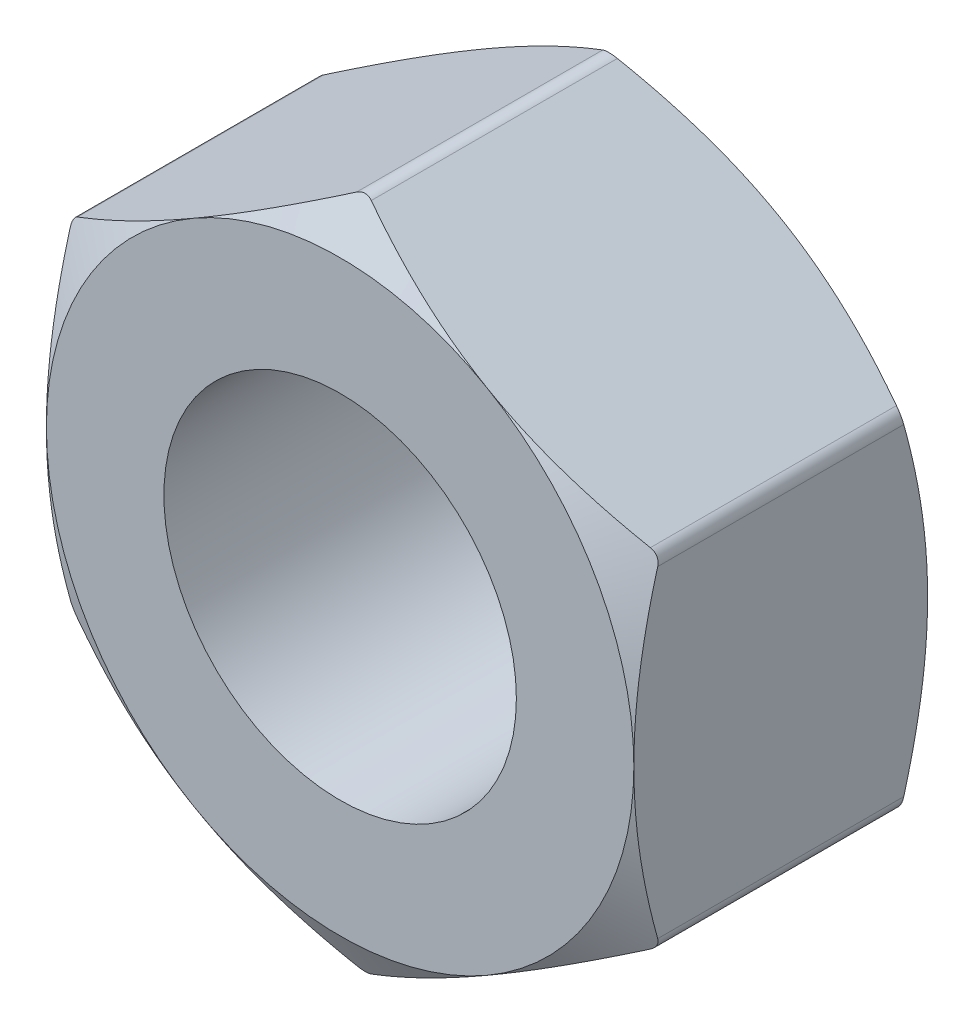
SolidWorks part; units mm, degrees
ref_plane "Front" through (0, 0, 0) normal (0, 0, 1) x (1, 0, 0)
ref_plane "Top" through (0, 0, 0) normal (0, 1, 0) x (1, 0, 0)
ref_plane "Right" through (0, 0, 0) normal (1, 0, 0) x (0, 0, -1)
sketch "Sketch1" plane through (0, 0, 0) normal (0, 0, 1) x (1, 0, 0)
  line L0 (0, 3) -> (0, 2) construction
  line L1 (-5, 2.8868) -> (-5, -2.8868)
  line L2 (-5, -2.8868) -> (0, -5.7735)
  line L3 (0, -5.7735) -> (5, -2.8868)
  line L4 (5, -2.8868) -> (5, 2.8868)
  line L5 (5, 2.8868) -> (0, 5.7735)
  line L6 (0, 5.7735) -> (-5, 2.8868)
  circle A0 centre (0, 0) radius 5 construction
  circle A1 centre (0, 0) radius 3 construction
  point P10 (0, 3)
  dimension "Width" = 10
  dimension "Thread Size" = 6
  dimension "Thread Pitch" = 1
sketch "Sketch2" plane through (0, 0, 0) normal (1, 0, 0) x (0, 0, -1)
  line L0 (-2.5, 0) -> (2.5, 0) construction
  line L1 (-2.5, 5.7735) -> (2.5, 5.7735) construction
  dimension "Height" = 5
sketch "Sketch15" plane through (0, 0, 0) normal (0, 0, 1) x (1, 0, 0)
  line L1 (0, 5.7735) -> (-5, 2.8868)
  line L2 (-5, 2.8868) -> (-5, -2.8868)
  line L3 (-5, -2.8868) -> (0, -5.7735)
  line L4 (0, -5.7735) -> (5, -2.8868)
  line L5 (5, -2.8868) -> (5, 2.8868)
  line L6 (5, 2.8868) -> (0, 5.7735)
  circle A0 centre (0, 0) radius 5 construction
extrude "Boss-Extrude2" add sketch "Sketch15" along normal mid plane 5
sketch "Sketch16" plane through (0, 0, 0) normal (0, 0, 1) x (1, 0, 0)
  circle A0 centre (0, 0) radius 3 construction
  circle A1 centre (0, 0) radius 3
sketch "Sketch4" [suppressed] plane through (0, 0, -2.5) normal (0, 0, -1) x (-1, 0, 0)
  circle A0 centre (0, 0) radius 3 construction
  circle A1 centre (0, 0) radius 3
extrude "Cut-Extrude4" cut sketch "Sketch16" against normal through all both and the other way through all
sketch "Sketch7" plane through (0, 0, 2.5) normal (0, 0, 1) x (1, 0, 0)
  circle A0 centre (0, 0) radius 5 construction
  circle A1 centre (0, 0) radius 5
extrude "Cut-Extrude5" cut sketch "Sketch7" against normal through all draft 60 flip side to cut
mirror "Mirror4" about plane through (0, 0, 0) normal (0, 0, 1) of "Cut-Extrude5"
fillet "Fillet2" radius 0.25 6 edges at (-5, 2.8868, 0) (-5, -2.8868, 0) (0, -5.7735, 0) (5, -2.8868, 0) (5, 2.8868, 0) (0, 5.7735, 0)
sketch "Sketch8" plane through (0, 0, 2.5) normal (0, 0, 1) x (1, 0, 0)
  line L0 (0.7765, -2.8978) -> (0, 0) construction
  line L2 (0, 3) -> (0, 2) construction
  circle A0 centre (0, 0) radius 3 construction
  point P0 (0.7765, -2.8978)
  dimension "D1" = 15
sketch "Sketch13" [suppressed] plane through (0, 0, -2.5) normal (0, 0, -1) x (-1, 0, 0)
  circle A0 centre (0, 0) radius 3 construction
  circle A1 centre (0, 0) radius 3
extrude "Boss-Extrude1" [suppressed] add sketch "Sketch13" against normal up to surface (5 mm away) separate body
curve "Helix/Spiral3" [suppressed] pitch 1 height 7 turns 7
sketch "Sketch12" [suppressed] plane through (0, 0, 0) normal (1, 0, 0) x (0, 0, -1)
  line L0 (3.375, 3) -> (2.5, 3)
  line L1 (3.375, 3) -> (3, 2.3505)
  line L2 (3, 2.3505) -> (2.875, 2.3505)
  line L3 (2.875, 2.3505) -> (2.5, 3)
  line L4 (2.9375, 2.3505) -> (2.9375, 3) construction
  line L5 (2.6875, 2.6752) -> (3.1875, 2.6752) construction
  dimension "D1" = 60
  dimension "D2" = 0.125
  dimension "D3" = 0.5
sweep "Cut-Sweep1" [suppressed] cut profiles "Sketch12" path "Helix/Spiral3"
sketch "Sketch17" [suppressed] plane through (0, 0, 2.5) normal (0, 0, 1) x (1, 0, 0)
  circle A1 centre (0, 0) radius 3
  circle A2 centre (0, 0) radius 3
  dimension "D1" = 0
extrude "Boss-Extrude3" [suppressed] add sketch "Sketch17" against normal up to surface (5 mm away)
combine bodies "Combine1" [suppressed] operation type add bodies to combine 127 118
sketch "Sketch10" [suppressed] plane through (0, 0, 2.5) normal (0, 0, 1) x (1, 0, 0)
  circle A0 centre (0, 0) radius 3 construction
  circle A1 centre (0, 0) radius 3 construction
  circle A2 centre (0, 0) radius 3.1
extrude "Cut-Extrude2" [suppressed] cut sketch "Sketch10" against normal through all draft 45
sketch "Sketch11" [suppressed] plane through (0, 0, -2.5) normal (0, 0, -1) x (-1, 0, 0)
  circle A1 centre (0, 0) radius 3.1 construction
  circle A2 centre (0, 0) radius 3.1
extrude "Cut-Extrude3" [suppressed] cut sketch "Sketch11" against normal through all draft 45
equation "\"D1\"= \"Height@Sketch2\""
equation "\"D3@Helix/Spiral3\"=\"Height@Sketch2\"+\"Thread Pitch@Sketch1\"*2"
equation "\"D4@Helix/Spiral3\"=\"Thread Pitch@Sketch1\""
equation "\"D2@Sketch12\" = \"D4@Helix/Spiral3\"*.125"
equation "\"D3@Sketch12\" = \"D4@Helix/Spiral3\"*.50"
equation "\"D1@Boss-Extrude2\"=\"Height@Sketch2\""
equation "\"D1@Fillet2\"=\"Width@Sketch1\"*0.025"
equation "\"D1@Sketch10\"=\"Thread Pitch@Sketch1\"*0.1"
